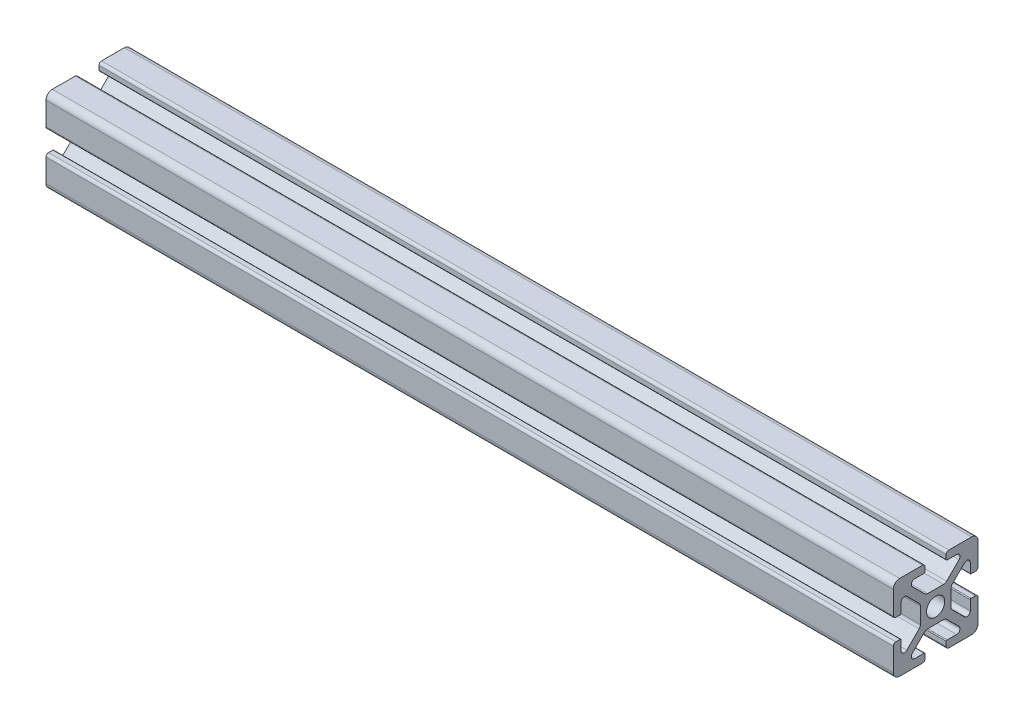
SolidWorks part; units mm, degrees
ref_plane "Front Plane" through (0, 0, 0) normal (0, 0, 1) x (1, 0, 0)
ref_plane "Top Plane" through (0, 0, 0) normal (0, 1, 0) x (1, 0, 0)
ref_plane "Right Plane" through (0, 0, 0) normal (1, 0, 0) x (0, 0, -1)
sketch "Sketch1" plane through (0, 0, 0) normal (1, 0, 0) x (0, 0, -1)
  line L0 (0, -10) -> (0, 10) construction
  line L1 (10, -10) -> (-10, -10)
  line L2 (10, -10) -> (10, 10)
  line L3 (10, 10) -> (0, 10)
  line L4 (-10, -10) -> (-10, 10)
  line L5 (10, -10) -> (-10, 10) construction
  line L6 (10, 10) -> (-10, -10) construction
  line L7 (10, 0) -> (-10, 0) construction
  line L8 (-2.5, 9.4) -> (-2.5, 8.3731)
  line L9 (-2.7, 8.1731) -> (-4.95, 8.1731)
  line L10 (-5.5157, 6.8075) -> (-2.6011, 3.8929)
  line L11 (-1.894, 3.6) -> (0, 3.6)
  line L12 (-5.3502, 4.0584) -> (-4.0584, 5.3502) construction
  line L13 (-3.825, 8.1731) -> (-3.825, 10) construction
  line L14 (-3.1, 10) -> (-10, 10)
  line L15 (-5.75, 7.3731) -> (5.75, 7.3731) construction
  circle A0 centre (0, 0) radius 2.15
  arc A1 (-4.95, 8.1731) -> (-5.5157, 6.8075) centre (-4.95, 7.3731) ccw
  arc A2 (-2.6011, 3.8929) -> (-1.894, 3.6) centre (-1.894, 4.6) ccw
  arc A3 (-2.5, 8.3731) -> (-2.7, 8.1731) centre (-2.7, 8.3731) cw
  arc A4 (-2.5, 9.4) -> (-3.1, 10) centre (-3.1, 9.4) ccw
  point P0 (0, 0)
  point P9 (0, 0)
  point P12 (0, 0)
  point P22 (-4.7043, 4.7043)
  point P32 (-2.5, 10)
  point P33 (-2.5, 8.8866)
  point P35 (-4.0584, 5.3502)
  point P37 (0, 7.3731)
  dimension "Center Hole Diameter" = 4.3
  dimension "D4" = 1
  dimension "D5" = 0.2
  dimension "D6" = 0.6
  dimension "D3" = 0.8
  dimension "Rail Height" = 20
  dimension "D7" = 6.4
  dimension "T Slot Width" = 5
  dimension "D10" = 10
  dimension "Rail Width" = 20
  dimension "D2" = 11.5
sketch "Sketch2" plane through (0, 0, 0) normal (0, 0, 1) x (1, 0, 0)
  line L0 (-132.4, 10) -> (-132.4, -10) construction
  line L1 (152.4, -10) -> (-152.4, -10) construction
  line L2 (152.4, -10) -> (152.4, 10) construction
  line L3 (152.4, 10) -> (-152.4, 10) construction
  line L4 (-152.4, -10) -> (-152.4, 10) construction
  line L5 (152.4, -10) -> (-152.4, 10) construction
  line L6 (152.4, 10) -> (-152.4, -10) construction
  line L7 (132.4, 10) -> (132.4, -10) construction
  point P0 (0, 0)
  point P12 (132.4, 0)
  dimension "Length" = 304.8
  dimension "D1" = 20
  dimension "D2" = 20
sketch "Sketch3" plane through (0, 0, 0) normal (1, 0, 0) x (0, 0, -1)
  line L0 (-5.5157, 6.8075) -> (-2.6011, 3.8929) construction
  line L5 (-3.1, 10) -> (-10, 10) construction
  line L6 (-2.5, 9.4) -> (-2.5, 8.3731) construction
  line L7 (-2.7, 8.1731) -> (-4.95, 8.1731) construction
  line L8 (-1.894, 3.6) -> (0, 3.6) construction
  line L9 (-5.5157, 6.8075) -> (-2.6011, 3.8929)
  line L10 (-10, 10) -> (0, 0) construction
  line L12 (-3.6, 1.894) -> (-3.6, 0)
  line L13 (-8.1731, 2.7) -> (-8.1731, 4.95)
  line L14 (-3.1, 10) -> (-8.5, 10)
  line L15 (-2.5, 9.4) -> (-2.5, 8.3731)
  line L16 (-2.7, 8.1731) -> (-4.95, 8.1731)
  line L17 (-1.894, 3.6) -> (0, 3.6)
  line L18 (-9.4, 2.5) -> (-8.3731, 2.5)
  line L19 (-10, 3.1) -> (-10, 8.5)
  line L20 (-6.8075, 5.5157) -> (-3.8929, 2.6011)
  line L21 (-3.6, 0) -> (-2.15, 0)
  line L22 (0, 3.6) -> (0, 2.15)
  arc A0 (-2.5, 9.4) -> (-3.1, 10) centre (-3.1, 9.4) ccw construction
  arc A1 (-2.7, 8.1731) -> (-2.5, 8.3731) centre (-2.7, 8.3731) ccw construction
  arc A2 (-4.95, 8.1731) -> (-5.5157, 6.8075) centre (-4.95, 7.3731) ccw construction
  arc A3 (-2.6011, 3.8929) -> (-1.894, 3.6) centre (-1.894, 4.6) ccw construction
  arc A4 (-2.5, 9.4) -> (-3.1, 10) centre (-3.1, 9.4) ccw
  arc A5 (-2.7, 8.1731) -> (-2.5, 8.3731) centre (-2.7, 8.3731) ccw
  arc A6 (-4.95, 8.1731) -> (-5.5157, 6.8075) centre (-4.95, 7.3731) ccw
  arc A7 (-2.6011, 3.8929) -> (-1.894, 3.6) centre (-1.894, 4.6) ccw
  arc A8 (-3.8929, 2.6011) -> (-3.6, 1.894) centre (-4.6, 1.894) cw
  arc A9 (-8.1731, 4.95) -> (-6.8075, 5.5157) centre (-7.3731, 4.95) cw
  arc A10 (-8.1731, 2.7) -> (-8.3731, 2.5) centre (-8.3731, 2.7) cw
  arc A11 (-9.4, 2.5) -> (-10, 3.1) centre (-9.4, 3.1) cw
  circle A12 centre (0, 0) radius 2.15 construction
  arc A13 (0, 2.15) -> (-2.15, 0) centre (0, 0) ccw
  arc A14 (-10, 8.5) -> (-8.5, 10) centre (-8.5, 8.5) cw
  dimension "D1" = 1.5
extrude "Boss-Extrude1" add sketch "Sketch3" against normal blind 100 and the other way blind 100
mirror "Mirror1" about plane through (0, 0, 0) normal (0, 1, 0) of bodies 104
mirror "Mirror2" about plane through (0, 0, 0) normal (0, 0, 1) of bodies 105
equation "\"D10@Sketch1\" = \"Rail Height@Sketch1\" / 2"
equation "\"D2@Sketch2\"=\"D1@Sketch2\""
